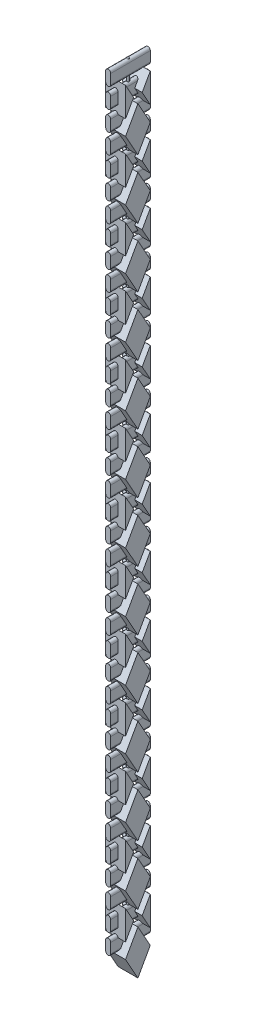
SolidWorks part; units mm, degrees
ref_plane "Front" through (0, 0, 0) normal (0, 0, 1) x (1, 0, 0)
ref_plane "Top" through (0, 0, 0) normal (0, 1, 0) x (1, 0, 0)
ref_plane "Right" through (0, 0, 0) normal (1, 0, 0) x (0, 0, -1)
sketch "Sketch1" plane through (0, 0, 0) normal (1, 0, 0) x (0, 0, -1)
  line L3 (9.525, 0) -> (25.4, 28.3519)
  line L4 (9.525, 0) -> (25.4, -28.3519)
  line L5 (25.4, 28.3519) -> (41.275, 0)
  line L9 (25.4, -28.3519) -> (41.275, 0)
  line L19 (0, 92.4304) -> (0, 0) construction
  line L20 (0, 0) -> (50.8, 0) construction
  line L21 (50.8, 0) -> (50.8, 91.9386) construction
  line L22 (9.525, 19.4963) -> (9.525, 56.7037)
  line L23 (9.525, 56.7037) -> (19.9418, 38.1)
  line L24 (19.9418, 38.1) -> (9.525, 19.4963)
  line L25 (9.525, 76.2) -> (25.4, 104.5519) construction
  line L26 (9.525, 76.2) -> (25.4, 47.8481) construction
  line L27 (25.4, 104.5519) -> (41.275, 76.2) construction
  line L28 (25.4, 47.8481) -> (41.275, 76.2) construction
  line L29 (41.275, 56.7037) -> (41.275, 19.4963)
  line L30 (41.275, 19.4963) -> (30.8582, 38.1)
  line L31 (30.8582, 38.1) -> (41.275, 56.7037)
  dimension "D1" = 50.8
  dimension "D2" = 9.525
  dimension "D3" = 9.525
  dimension "D4" = 9.525
  dimension "D5" = 9.525
  dimension "D6" = 76.2
extrude "Boss-Extrude1" add sketch "Sketch1" along normal blind 25.4
sketch "Sketch2" plane through (0, 0, 0) normal (0, 0, 1) x (1, 0, 0)
  line L0 (12.7, 6.35) -> (12.7, 19.05) construction
  line L1 (9.525, 6.35) -> (9.525, 19.05)
  line L2 (15.875, 6.35) -> (15.875, 19.05)
  line L3 (12.7, 31.75) -> (12.7, 44.45) construction
  line L4 (9.525, 31.75) -> (9.525, 44.45)
  line L5 (15.875, 31.75) -> (15.875, 44.45)
  line L6 (12.7, 57.15) -> (12.7, 69.85) construction
  line L7 (9.525, 57.15) -> (9.525, 69.85)
  line L8 (15.875, 57.15) -> (15.875, 69.85)
  arc A0 (9.525, 6.35) -> (15.875, 6.35) centre (12.7, 6.35) ccw
  arc A1 (15.875, 19.05) -> (9.525, 19.05) centre (12.7, 19.05) ccw
  arc A2 (9.525, 31.75) -> (15.875, 31.75) centre (12.7, 31.75) ccw
  arc A3 (15.875, 44.45) -> (9.525, 44.45) centre (12.7, 44.45) ccw
  arc A4 (9.525, 57.15) -> (15.875, 57.15) centre (12.7, 57.15) ccw
  arc A5 (15.875, 69.85) -> (9.525, 69.85) centre (12.7, 69.85) ccw
  point P2 (12.7, 12.7)
  point P12 (12.7, 38.1)
  point P19 (12.7, 63.5)
  dimension "D3" = 6.35
  dimension "D6" = 25.4
  dimension "D1" = 6.35
  dimension "D2" = 12.7
  dimension "D4" = 12.7
  dimension "D5" = 3
extrude "Boss-Extrude2" add sketch "Sketch2" against normal blind 50.8
pattern_linear "LPattern1" count 13 spacing 76.2 along (0, 1, 0) of bodies 168 109 110 108
sketch "Sketch3" plane through (0, 0, 0) normal (0, 1, 0) x (1, 0, 0)
  circle A0 centre (12.7, 25.4) radius 1.5875
  dimension "D1" = 3.175
  dimension "D3" = 12.7
  dimension "D2" = 25.4
extrude "Boss-Extrude3" add sketch "Sketch3" along normal through all
